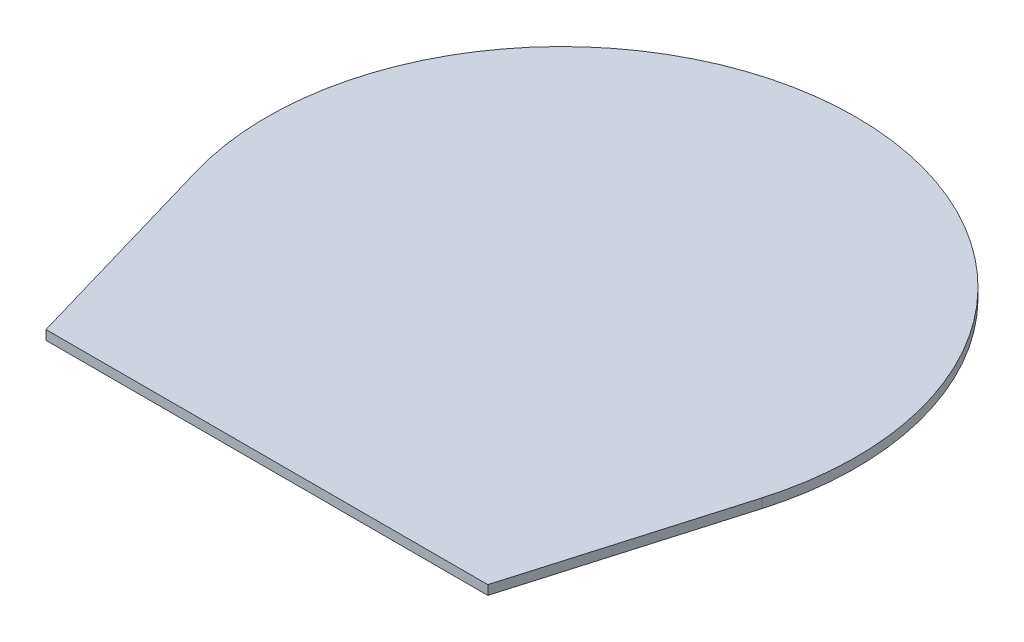
SolidWorks part; units mm, degrees
ref_plane "Front Plane" through (0, 0, 0) normal (0, 0, 1) x (1, 0, 0)
ref_plane "Top Plane" through (0, 0, 0) normal (0, 1, 0) x (1, 0, 0)
ref_plane "Right Plane" through (0, 0, 0) normal (1, 0, 0) x (0, 0, -1)
sketch "Sketch1" plane through (0, 0, 0) normal (0, 1, 0) x (1, 0, 0)
  circle A0 centre (0, 0) radius 100
  dimension "D1" = 200
extrude "Boss-Extrude1" add sketch "Sketch1" along normal blind 3.175
sketch "Sketch4" plane through (0, 0, 0) normal (0, 1, 0) x (1, 0, 0)
  line L0 (-75, -100) -> (0, -100)
  line L1 (-75, -100) -> (-96, -28)
  line L2 (0, 0) -> (0, -53.2962) construction
  line L3 (75, -100) -> (96, -28)
  line L4 (75, -100) -> (0, -100)
  circle A0 centre (0, 0) radius 100 construction
  arc A1 (-96, -28) -> (0, -100) centre (0, 0) ccw
  arc A2 (96, -28) -> (0, -100) centre (0, 0) cw
  point P2 (0, -105)
  point P7 (0, -105)
  point P8 (-22.377, -102.5879)
  point P12 (0, 0)
  dimension "D1" = 150
extrude "Boss-Extrude2" add sketch "Sketch4" along normal up to surface (3.175 mm away) contours A1 L1 L0 | L3 A2 L4 region at (-63.3809, 0, 84.5079) region at (63.3809, 0, 84.5079) up to face at (0, 3.175, 100)
